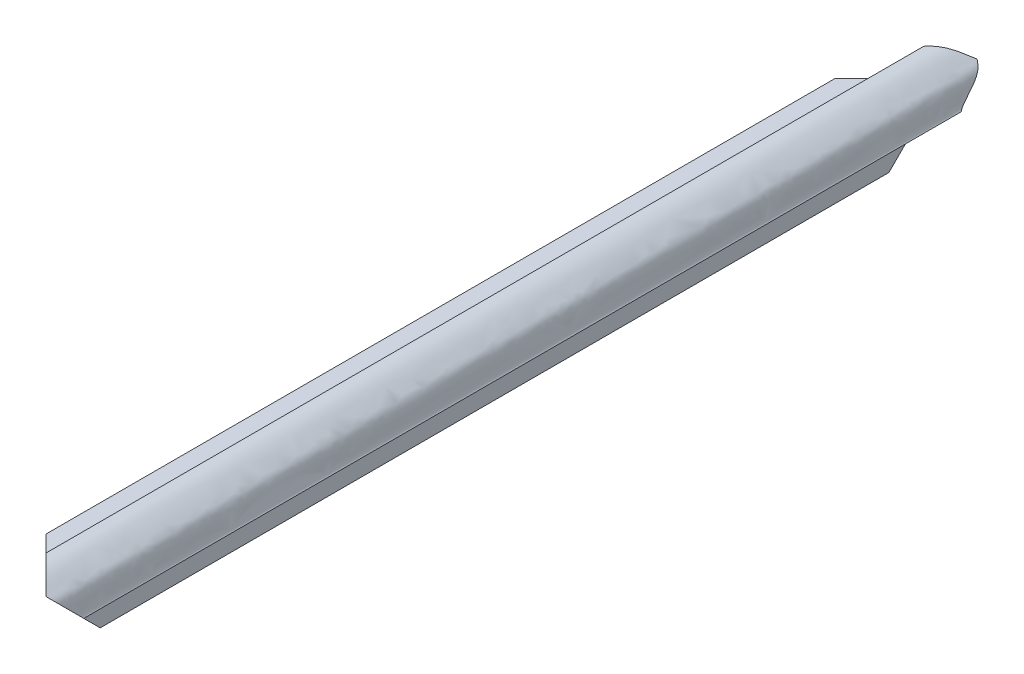
SolidWorks part; units mm, degrees
ref_plane "Front Plane" through (0, 0, 0) normal (0, 0, 1) x (1, 0, 0)
ref_plane "Top Plane" through (0, 0, 0) normal (0, 1, 0) x (1, 0, 0)
ref_plane "Right Plane" through (0, 0, 0) normal (1, 0, 0) x (0, 0, -1)
ref_axis "Axis1" through (0, 0, -88.99) along (0, 0, 1)
sketch "Sketch16" plane through (0, 0, 0) normal (0, 1, 0) x (1, 0, 0)
  line L0 (0, -49.53) -> (0, 49.53) construction
  point P2 (0, 0)
  dimension "D1" = 99.06
sketch "Sketch2" plane through (0, 0, 0) normal (0, 0, 1) x (1, 0, 0)
  line L0 (-7.3025, -1.5) -> (-2.54, -1.5) construction
  line L1 (-7.3025, -1.5) -> (-7.3025, 1.5) construction
  line L2 (-2.54, -1.5) -> (-2.54, 1.5) construction
  line L3 (-7.3025, 1.5) -> (-2.54, 1.5) construction
  line L4 (-2.54, 0) -> (0, 0) construction
  line L5 (0, 0) -> (0, -2.54) construction
  line L6 (-1.5, -2.54) -> (1.5, -2.54) construction
  line L7 (-1.5, -2.54) -> (-1.5, -7.3025) construction
  line L8 (1.5, -2.54) -> (1.5, -7.3025) construction
  line L9 (-1.5, -7.3025) -> (1.5, -7.3025) construction
  point P7 (0, -2.54)
  point P16 (1.5, 1.5)
  dimension "D1" = 3
  dimension "D2" = 4.7625
  dimension "D3" = 2.54
  dimension "D4" = 90
ref_plane "Plane1" through (0, 0, 0) normal (-1, 0, 0) x (0, -1, 0)
sketch "Sketch7" plane through (0, 0, 0) normal (0, 0, 1) x (1, 0, 0)
  line L0 (-7.3025, -1.5) -> (-2.54, -1.5)
  line L1 (-7.3025, -1.5) -> (-7.3025, -3.6212)
  line L2 (-2.54, -1.5) -> (-2.54, -3.6212)
  line L3 (-7.3025, -3.6212) -> (-2.54, -3.6212)
  dimension "D1" = 2.1212
extrude "Boss-Extrude2" add sketch "Sketch7" along normal mid plane 105.41 separate body
sketch "Sketch8" plane through (0, 0, 0) normal (0, 0, 1) x (1, 0, 0)
  line L0 (-1.5, -2.54) -> (-1.5, -7.3025)
  line L1 (-1.5, -2.54) -> (-3.6212, -2.54)
  line L2 (-1.5, -7.3025) -> (-3.6212, -7.3025)
  line L3 (-3.6212, -2.54) -> (-3.6212, -7.3025)
  line L4 (-2.54, -3.6212) -> (-2.54, -1.5) construction
extrude "Boss-Extrude3" add sketch "Sketch8" along normal mid plane 105.41
sketch "Sketch11" plane through (0, 0, 0) normal (0, 0, 1) x (1, 0, 0)
  line L0 (-2.54, 1.5) -> (-2.54, -1.5)
  line L1 (-2.54, -1.5) -> (-7.3025, -1.5)
  line L2 (-7.3025, -1.5) -> (-7.3025, -3.6212)
  line L3 (-7.3025, -3.6212) -> (-5.8663, -3.6212)
  line L4 (-7.3025, -3.6212) -> (-3.6212, -3.6212) construction
  line L5 (-5.8663, -3.6212) -> (-3.6212, -5.8663)
  line L6 (-3.6212, -3.6212) -> (-3.6212, -7.3025) construction
  line L7 (-3.6212, -5.8663) -> (-3.6212, -7.3025)
  line L8 (-3.6212, -7.3025) -> (-1.5, -7.3025)
  line L9 (-1.5, -7.3025) -> (-1.5, -2.54)
  line L10 (-1.5, -2.54) -> (1.5, -2.54)
  line L11 (-2.54, -0.52) -> (-1.1116, -1.1116) construction
  line L12 (-1.1116, -1.1116) -> (-0.52, -2.54) construction
  line L13 (-2.54, 1.5) -> (-2.54, -2.54) construction
  line L14 (-2.54, -2.54) -> (1.5, -2.54) construction
  line L15 (-2.54, -2.54) -> (0.3167, 0.3167) construction
  line L16 (-2.54, -0.52) -> (-0.52, -2.54) construction
  line L17 (-2.54, -2.54) -> (-0.994, 1.1925) construction
  line L18 (-2.54, -2.54) -> (1.1925, -0.994) construction
  spline S1 degree 3 poles (-2.54, 1.5) (-1.2956, 1.6355) (-0.0425, 0.4732) (1.2977, -0.2922) (1.2637, -2.3404) (1.5, -2.54) knots 0 0 0 0 0.496687 0.741347 0.89974 0.89974 0.89974 0.89974
  dimension "D1" = 3.175
extrude "Boss-Extrude4" add sketch "Sketch11" along normal mid plane 105.41
sketch "Sketch14" plane through (0, 0, 0) normal (0, 1, 0) x (1, 0, 0)
  line L0 (-7.3025, -42.2275) -> (-7.3025, -56.8325)
  line L1 (-7.3025, -52.705) -> (-7.3025, 52.705) construction
  line L2 (-7.3025, -56.8325) -> (7.3025, -56.8325)
  line L4 (7.3025, -56.8325) -> (-7.3025, -42.2275)
  line L5 (0, 88.99) -> (0, -88.99) construction
  line L6 (0, -49.53) -> (0, 49.53) construction
  line L8 (-7.3025, 42.2275) -> (7.3025, 56.8325)
  line L9 (7.3025, 56.8325) -> (-7.3025, 56.8325)
  line L10 (-7.3025, 56.8325) -> (-7.3025, 42.2275)
  point P5 (0, -49.53)
  point P13 (0, 49.53)
  dimension "D2" = 45
  dimension "D1" = 45
extrude "Cut-Extrude4" cut sketch "Sketch14" against normal through all both and the other way through all
sketch "Sketch17" plane through (0, 0, 0) normal (-1, 0, 0) x (0, -1, 0)
  line L0 (7.3025, 56.8325) -> (7.3025, 42.2275)
  line L2 (7.3025, 42.2275) -> (-7.3025, 56.8325)
  line L3 (-7.3025, 56.8325) -> (7.3025, 56.8325)
  line L4 (7.3025, -42.2275) -> (-7.3025, -56.8325)
  line L5 (-7.3025, -56.8325) -> (7.3025, -56.8325)
  line L6 (7.3025, -56.8325) -> (7.3025, -42.2275)
  point P4 (0, 49.53)
  point P10 (0, -49.53)
  dimension "D2" = 45
  dimension "D1" = 45
  dimension "D3" = 7.3025
extrude "Cut-Extrude5" cut sketch "Sketch17" against normal through all both and the other way through all
ref_plane "Midplane" through (0, 0, 0) normal (-0.7071, 0.7071, 0) x (0.7071, 0.7071, 0)
equation "\"plate_thickness\"= 3mm"
equation "\"D1@Sketch2\"=\"plate_thickness\""
equation "\"joiner_lip_width\" = 0.1875"
equation "\"D2@Sketch2\"=\"joiner_lip_width\""
equation "\"face_gap\"=0.1"
equation "\"D3@Sketch2\"=\"face_gap\""
equation "\"inside_angle\"= 90"
equation "\"joiner_thickness\"= 0.0835128"
equation "\"edge_length\"= 3.9"
equation "\"Face1_TopLip\"= 90deg"
equation "\"Face1_BottomLip\"= 90deg"
equation "\"Face2_TopLip\"= 90deg"
equation "\"Face2_BottomLip\"= 90deg"
equation "\"D1@Sketch7\"=\"joiner_thickness\""
equation "\"D1@Boss-Extrude2\"=\"Extrude_to\""
equation "\"D1@Boss-Extrude3\"=\"Extrude_to\""
equation "\"D1@Boss-Extrude4\"=\"Extrude_to\""
equation "\"D4@Sketch2\"=\"inside_angle\""
equation "\"Extrude_to\"= \"edge_length\" + .25"
equation "\"D2@Sketch14\"=\"Face1_BottomLip\"/2"
equation "\"D1@Sketch16\"=\"edge_length\""
equation "\"D1@Sketch14\"=\"Face1_TopLip\"/2"
equation "\"D1@Sketch17\"=\"Face2_TopLip\"/2"
equation "\"D2@Sketch17\"=\"Face2_BottomLip\"/2"
equation "\"D3@Sketch17\"=\"joiner_lip_width\"+\"face_gap\""
equation "\"D2@Sketch5\"=\"Face2_TopLip\"/2"
equation "\"D1@Sketch5\"=\"Face2_BottomLip\"/2"
equation "\"D2@Sketch4\"=\"Face1_TopLip\"/2"
equation "\"D1@Sketch4\"=\"Face1_BottomLip\"/2"
equation "\"D1\" = \"edge_length\""
equation "\"D2@Sketch12\"=\"Face1_TopLip\"/2"
equation "\"D1@Sketch12\"=\"Face1_BottomLip\"/2"
